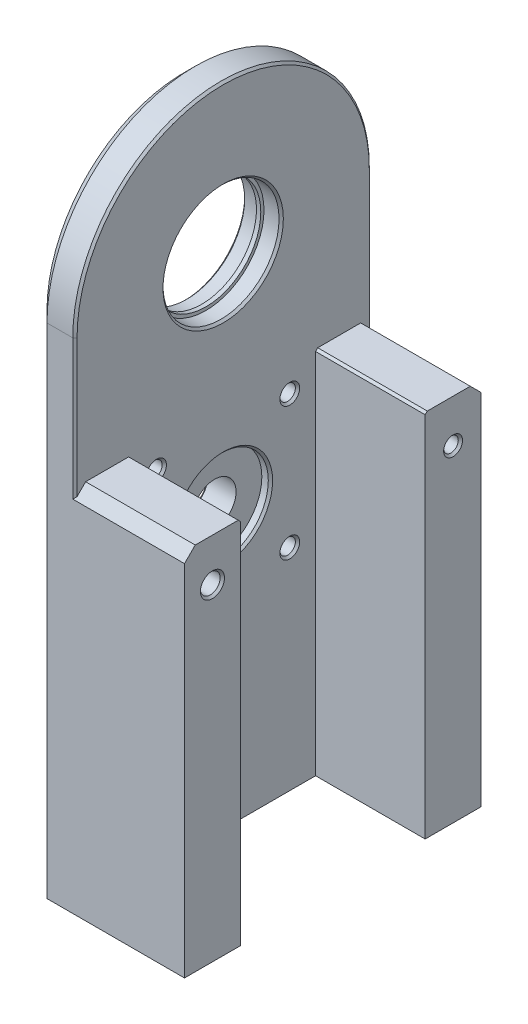
SolidWorks part; units mm, degrees
ref_plane "Ebene vorne" through (0, 0, 0) normal (0, 0, 1) x (1, 0, 0)
ref_plane "Ebene oben" through (0, 0, 0) normal (0, 1, 0) x (1, 0, 0)
ref_plane "Ebene rechts" through (0, 0, 0) normal (1, 0, 0) x (0, 0, -1)
sketch "Sketch2" plane through (0, 0, 0) normal (1, 0, 0) x (0, 0, -1)
  line L1 (0, 0) -> (69, 0)
  line L2 (0, 0) -> (0, 86)
  line L3 (0, 86) -> (69, 86)
  line L4 (69, 0) -> (69, 86)
  line L5 (0, 0) -> (69, 86) construction
  line L6 (0, 86) -> (69, 0) construction
  line L7 (0, 86) -> (69, 86)
  line L8 (0, 86) -> (0, 116)
  line L9 (0, 116) -> (69, 116)
  line L10 (69, 86) -> (69, 116)
  line L11 (0, 86) -> (69, 116) construction
  line L12 (0, 116) -> (69, 86) construction
  circle A0 centre (34.5, 116) radius 34.5
  circle A1 centre (34.5, 116) radius 12.75
  point P4 (34.5, 43)
  point P9 (34.5, 101)
  dimension "D4" = 25.5
  dimension "D1" = 69
  dimension "D2" = 86
  dimension "D3" = 30
extrude "Boss-Extrude1" add sketch "Sketch2" along normal blind 34.5 contours A0 L3 L2 L1 L4 | L7 A0 region at (0, 42.2679, -34.5) region at (0, 84.1895, -34.5)
sketch "Sketch9" plane through (34.5, 0, 0) normal (1, 0, 0) x (0, 0, -1)
  line L0 (13, 86) -> (13, 0)
  line L1 (0, 86) -> (69, 86) construction
  line L2 (0, 0) -> (69, 0) construction
  line L3 (13, 0) -> (56, 0)
  line L4 (56, 0) -> (56, 86)
  line L5 (56, 86) -> (13, 86)
  line L6 (0, 0) -> (0, 86) construction
  line L7 (69, 0) -> (69, 86) construction
  line L9 (13, 0) -> (56, 0)
  line L10 (13, 0) -> (13, 43)
  line L11 (13, 43) -> (56, 43)
  line L12 (56, 0) -> (56, 43)
  line L13 (13, 0) -> (56, 43) construction
  line L14 (13, 43) -> (56, 0) construction
  line L15 (56, 43) -> (13, 43)
  line L16 (56, 43) -> (56, 86)
  line L17 (56, 86) -> (13, 86)
  line L18 (13, 43) -> (13, 86)
  line L19 (56, 43) -> (13, 86) construction
  line L20 (56, 86) -> (13, 43) construction
  circle A0 centre (34.5, 64.5) radius 11
  circle A1 centre (34.5, 64.5) radius 5
  point P15 (34.5, 21.5)
  point P19 (34.5, 64.5)
  line M2 (69, 86) -> (0, 86)
  line M4 (0, 0) -> (69, 0)
  dimension "D3" = 22
  dimension "D4" = 10
  dimension "D1" = 13
  dimension "D2" = 13
extrude "Cut-Extrude1" cut sketch "Sketch9" against normal offset from surface (25.5 mm away) 9 contours L0 L11 L4 A0 M2 | A0 A1 | A1 | L11 L0 L4 M4 region at (34.5, 85.3919, -34.5) region at (34.5, 21.5, -34.5) region at (34.5, 64.5, -23.8111) region at (34.5, 64.5, -34.5) up to face at (0, 43, -34.5)
extrude "Boss-Extrude2" add sketch "Sketch2<5>" along normal up to surface (9 mm away) contours L9 A0 L7 | A0 L8 L3 | A0 L3 L10 | L9 A0 region at (0, 93.069, -4.894) region at (0, 93.069, -64.106) region at (0, 100.9752, -34.5) region at (0, 132.1024, -34.5) up to face at (9, 43, -34.5)
sketch "Sketch2<5>" plane through (0, 0, 0) normal (1, 0, 0) x (0, 0, -1) same geometry as "Sketch2"
extrude "Cut-Extrude2" cut sketch "Sketch9<3>" against normal offset from surface (27.5 mm away) 2 contours A0 A1 | A1 region at (34.5, 64.5, -23.8111) region at (34.5, 64.5, -34.5) up to face at (9, 76.3125, -34.5) offset beyond the face yes
sketch "Sketch9<3>" plane through (34.5, 0, 0) normal (1, 0, 0) x (0, 0, -1) same geometry as "Sketch9"
extrude "Cut-Extrude3" cut sketch "Sketch9<4>" against normal through all contours A1 region at (34.5, 64.5, -34.5)
sketch "Sketch9<4>" plane through (34.5, 0, 0) normal (1, 0, 0) x (0, 0, -1) same geometry as "Sketch9"
sketch "Sketch20" plane through (9, 0, 0) normal (1, 0, 0) x (0, 0, -1)
  circle A0 centre (34.5, 116) radius 13.5
  dimension "D1" = 27
extrude "Cut-Extrude4" cut sketch "Sketch20" against normal blind 4
ref_plane "Plane1" through (4.5, 0, 0) normal (1, 0, 0) x (0, 0, -1)
mirror "Mirror1" about plane through (4.5, 0, 0) normal (1, 0, 0) of "Cut-Extrude4"
hole_wizard "CBORE for M3 Hex Socket Head Cap Screw1" positions "Sketch10" profile "Sketch11" counterbore size "M3" standard "DIN" end condition through all
sketch "Sketch10" plane through (0, 0, 0) normal (-1, 0, 0) x (0, 0, 1)
  line L1 (-50, 49) -> (-19, 49)
  line L2 (-50, 49) -> (-50, 80)
  line L3 (-50, 80) -> (-19, 80)
  line L4 (-19, 49) -> (-19, 80)
  line L5 (-50, 49) -> (-19, 80) construction
  line L6 (-50, 80) -> (-19, 49) construction
  point P1 (-34.5, 64.5)
  point P2 (-19, 80)
  point P5 (-50, 49)
  point P6 (-50, 80)
  point P7 (-19, 49)
  dimension "D1" = 31
sketch "Sketch11" plane through (0, 49, -19) normal (0, 1, 0) x (0, 0, 1)
  line L0 (0, 0) -> (0, 34.5)
  line L1 (0, 34.5) -> (1.8, 34.5)
  line L3 (1.8, 34.5) -> (1.8, 3.4)
  line L4 (1.8, 3.4) -> (3.25, 3.4)
  line L5 (3.25, 3.4) -> (3.25, 0)
  line L7 (3.25, 0) -> (0, 0)
  line L11 (0, -6.35) -> (0, 107.95) construction
  dimension "Thru Hole Dia." = 3.6
  dimension "Thru Hole Depth" = 34.5
  dimension "C'Bore Dia." = 6.5
  dimension "C'Bore Depth" = 3.4
hole_wizard "Ø4.6 (4.6) Diameter Hole1" positions "Sketch12" profile "Sketch13" hole size "Ø4.6" standard "DIN"
sketch "Sketch12" plane through (0, 0, 0) normal (0, -1, 0) x (-1, 0, 0)
  line L0 (-34.5, 69) -> (-34.5, 0) construction
  line L1 (-34.5, 0) -> (-34.5, 13) construction
  line L4 (-64.5, 6.5) -> (-4.5, 6.5)
  line L5 (-64.5, 6.5) -> (-64.5, 62.5)
  line L6 (-64.5, 62.5) -> (-4.5, 62.5)
  line L7 (-4.5, 6.5) -> (-4.5, 62.5)
  line L8 (-64.5, 6.5) -> (-4.5, 62.5) construction
  line L9 (-64.5, 62.5) -> (-4.5, 6.5) construction
  line L10 (-34.5, 69) -> (0, 69) construction
  line L11 (0, 0) -> (0, 69) construction
  point P6 (-34.5, 34.5)
  point P7 (-4.5, 62.5)
  point P12 (-4.5, 6.5)
  point P70 (-4.5, 34.5)
  dimension "D1" = 6.5
  dimension "D2" = 4.5
sketch "Sketch13" plane through (4.5, 0, -34.5) normal (1, 0, 0) x (0, 0, -1)
  line L0 (0, 0) -> (0, 7.382)
  line L1 (0, 7.382) -> (2.3, 6)
  line L2 (2.3, 6) -> (2.3, 0)
  line L5 (2.3, 0) -> (0, 0)
  line L10 (0, 7.382) -> (-2.3, 6) construction
  line L11 (0, -6.35) -> (0, 107.95) construction
  dimension "Hole Dia." = 4.6
  dimension "Hole Depth" = 6
  dimension "Drill Angle" = 118
hole_wizard "CBORE for M3 Hex Socket Head Cap Screw2" positions "Sketch16" profile "Sketch18" counterbore size "M3" standard "DIN" end condition through all
sketch "Sketch16" plane through (0, 0, 0) normal (-1, 0, 0) x (0, 0, 1)
  line L0 (-56, 86) -> (-69, 86) construction
  line L1 (-56, 86) -> (-69, 86)
  line L2 (-62.5, 86) -> (-62.5, 76) construction
  point P4 (-62.5, 76)
  dimension "D1" = 10
sketch "Sketch18" plane through (0, 76, -62.5) normal (0, 1, 0) x (0, 0, 1)
  line L0 (0, 0) -> (0, 34.5)
  line L1 (0, 34.5) -> (1.7, 34.5)
  line L3 (1.7, 34.5) -> (1.7, 3.4)
  line L4 (1.7, 3.4) -> (3.25, 3.4)
  line L5 (3.25, 3.4) -> (3.25, 0)
  line L7 (3.25, 0) -> (0, 0)
  line L11 (0, -6.35) -> (0, 107.95) construction
  dimension "Thru Hole Dia." = 3.4
  dimension "Thru Hole Depth" = 34.5
  dimension "C'Bore Dia." = 6.5
  dimension "C'Bore Depth" = 3.4
hole_wizard "Ø4.6 (4.6) Diameter Hole2" positions "Sketch14" profile "Sketch15" hole size "Ø4.6" standard "DIN"
sketch "Sketch14" plane through (34.5, 0, 0) normal (1, 0, 0) x (0, 0, -1)
  line L0 (6.5, 86) -> (6.5, 76) construction
  line L1 (0, 86) -> (13, 86) construction
  point P2 (6.5, 76)
  dimension "D1" = 10
sketch "Sketch15" plane through (34.5, 76, -6.5) normal (0, 1, 0) x (0, 0, -1)
  line L0 (0, 0) -> (0, 7.382)
  line L1 (0, 7.382) -> (2.3, 6)
  line L2 (2.3, 6) -> (2.3, 0)
  line L5 (2.3, 0) -> (0, 0)
  line L10 (0, 7.382) -> (-2.3, 6) construction
  line L11 (0, -6.35) -> (0, 107.95) construction
  dimension "Hole Dia." = 4.6
  dimension "Hole Depth" = 6
  dimension "Drill Angle" = 118
hole_wizard "Ø4.6 (4.6) Diameter Hole3" positions "Sketch21" profile "Sketch22" hole size "Ø4.6" standard "DIN"
sketch "Sketch21" plane through (0, 0, 0) normal (-1, 0, 0) x (0, 0, 1)
  line L0 (-34.5, 116) -> (-34.5, 64.5) construction
  point P5 (-9.5, 89.5)
  point P9 (-59.5, 89.5)
  dimension "D1" = 25
  dimension "D2" = 25
sketch "Sketch22" plane through (0, 89.5, -59.5) normal (0, 1, 0) x (0, 0, 1)
  line L0 (0, 0) -> (0, 6.382)
  line L1 (0, 6.382) -> (2.3, 5)
  line L2 (2.3, 5) -> (2.3, 0)
  line L5 (2.3, 0) -> (0, 0)
  line L10 (0, 6.382) -> (-2.3, 5) construction
  line L11 (0, -6.35) -> (0, 107.95) construction
  dimension "Hole Dia." = 4.6
  dimension "Hole Depth" = 5
  dimension "Drill Angle" = 118
chamfer "2,5mm Chamfer1" distance 2.5 angle 45 5 edges at (21.75, 86, -69) (21.75, 86, 0) (0, 58, -69) (0, 150.5, -34.5) (0, 58, 0)
chamfer "0,5mm Chamfer2" distance 0.5 angle 45 26 edges at (3.4, 49, -48.2) (9, 49, -51.8) (4.5, 0, -8.8) (4.5, 0, -36.8) (4.5, 0, -64.8) (9, 49, -20.8) (9, 64.5, -45.5) (34.5, 76, -8.8) (9, 80, -51.8) (34.5, 76, -60.8) (9, 80, -20.8) (0, 49, -15.75) (0, 49, -46.75) (0, 64.5, -39.5) (0, 76, -59.25) (0, 80, -46.75) (0, 80, -15.75) (21.75, 86, -13) (9, 99.75, -69) (9, 99.75, 0) (9, 150.5, -34.5) (0, 116, -48) (9, 116, -48) (21.75, 86, -56) (0, 89.5, -7.2) (0, 89.5, -57.2)
